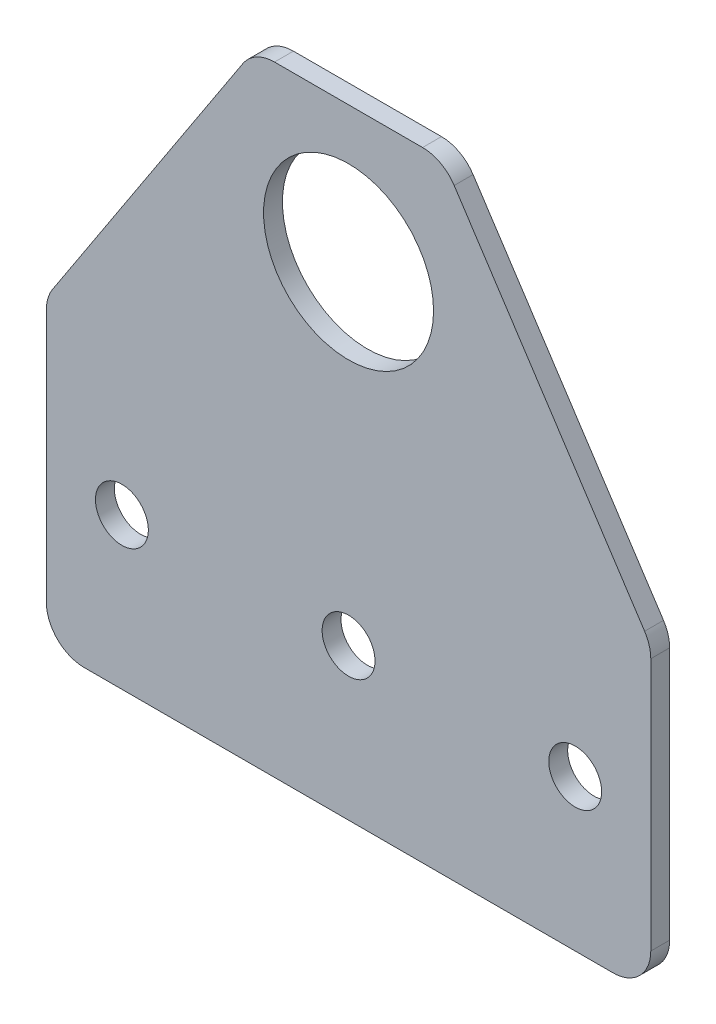
SolidWorks part; units mm, degrees
ref_plane "Plan de face" through (0, 0, 0) normal (0, 0, 1) x (1, 0, 0)
ref_plane "Plan de dessus" through (0, 0, 0) normal (0, 1, 0) x (1, 0, 0)
ref_plane "Plan de droite" through (0, 0, 0) normal (1, 0, 0) x (0, 0, -1)
sketch "Esquisse1" plane through (0, 0, 0) normal (0, 0, 1) x (1, 0, 0)
  line L0 (0, 0) -> (0, 82) construction
  line L1 (-40, 0) -> (40, 0)
  line L2 (40, 0) -> (40, 40)
  line L3 (40, 40) -> (12.5, 82)
  line L4 (12.5, 82) -> (-12.5, 82)
  line L5 (-40, 40) -> (-12.5, 82)
  line L6 (-40, 0) -> (-40, 40)
  line L7 (-40, 20) -> (40, 20) construction
  circle A0 centre (0, 64) radius 11.25
  circle A1 centre (0, 20) radius 3.5
  circle A2 centre (30, 20) radius 3.5
  circle A3 centre (-30, 20) radius 3.5
  dimension "D5" = 22.5
  dimension "D6" = 18
  dimension "D8" = 7
  dimension "D9" = 30
  dimension "D1" = 80
  dimension "D2" = 40
  dimension "D3" = 25
  dimension "D4" = 24
  dimension "D7" = 20
extrude "Boss.-Extru.1" add sketch "Esquisse1" along normal blind 2.5
fillet "Congé1" radius 5 6 edges at (12.5, 82, 1.25) (-12.5, 82, 1.25) (-40, 40, 1.25) (40, 40, 1.25) (40, 0, 1.25) (-40, 0, 1.25)
